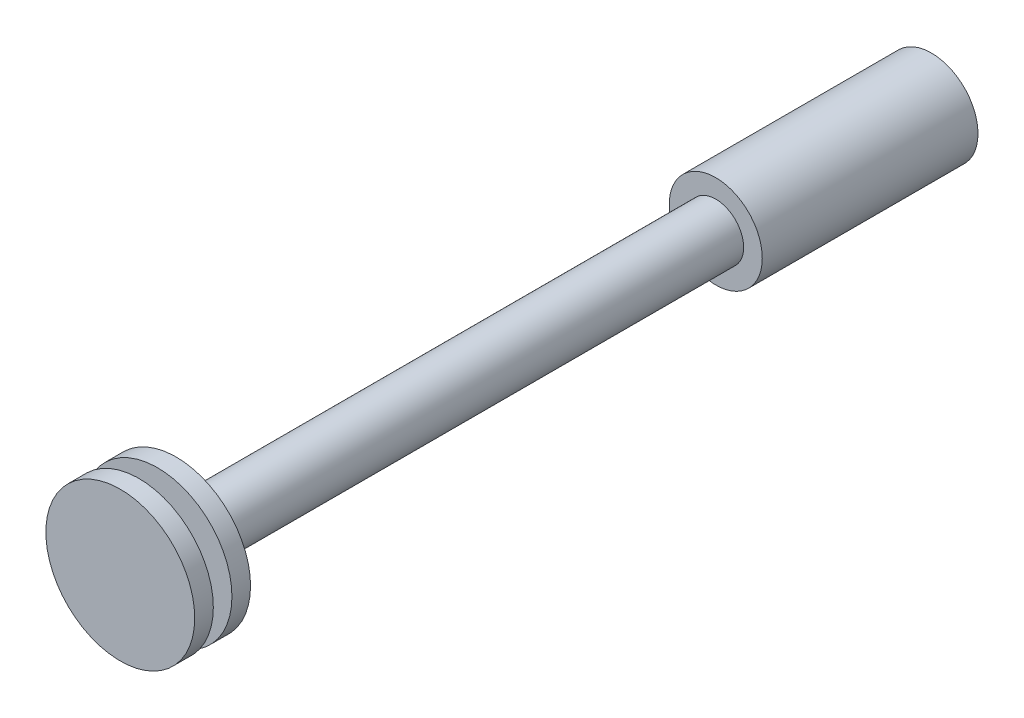
SolidWorks part; units mm, degrees
ref_plane "前视基准面" through (0, 0, 0) normal (0, 0, 1) x (1, 0, 0)
ref_plane "上视基准面" through (0, 0, 0) normal (0, 1, 0) x (1, 0, 0)
ref_plane "右视基准面" through (0, 0, 0) normal (1, 0, 0) x (0, 0, -1)
other "Configuration Table"
sketch "草图1" plane through (0, 0, 0) normal (0, 0, 1) x (1, 0, 0)
  circle A0 centre (0, 0) radius 3
extrude "凸台-拉伸1" add sketch "草图1" along normal blind 180
sketch "草图2" plane through (0, 0, 180) normal (0, 0, 1) x (1, 0, 0)
  circle A2 centre (0, 0) radius 8
  circle A3 centre (0, 0) radius 8
  dimension "D1" = 5
extrude "凸台-拉伸2" add sketch "草图2" against normal blind 2
extrude "凸台-拉伸3" add sketch "草图2<2>" along normal blind 2 from surface starting at face at (3, 0, 0)
sketch "草图2<2>" plane through (0, 0, 180) normal (0, 0, 1) x (1, 0, 0) same geometry as "草图2"
extrude "凸台-拉伸4" add sketch "草图1<2>" against normal blind 2
sketch "草图1<2>" plane through (0, 0, 0) normal (0, 0, 1) x (1, 0, 0) same geometry as "草图1"
extrude "凸台-拉伸5" add sketch "草图1<3>" along normal blind 2 from surface starting at face at (8, 0, 180)
sketch "草图1<3>" plane through (0, 0, 0) normal (0, 0, 1) x (1, 0, 0) same geometry as "草图1"
extrude "凸台-拉伸6" add sketch "草图2<3>" along normal blind 2 from surface starting at face at (3, 0, 182)
sketch "草图2<3>" plane through (0, 0, 180) normal (0, 0, 1) x (1, 0, 0) same geometry as "草图2"
extrude "凸台-拉伸7" add sketch "草图2<4>" against normal blind 2 from surface starting at face at (3, 0, -2)
sketch "草图2<4>" plane through (0, 0, 180) normal (0, 0, 1) x (1, 0, 0) same geometry as "草图2"
sketch "草图3" plane through (0, 0, 184) normal (0, 0, 1) x (1, 0, 0)
  circle A0 centre (0, 0) radius 5
extrude "凸台-拉伸10" add sketch "草图3" against normal blind 60 from offset 64 offset against normal yes
sketch "草图4" plane through (0, 0, 0) normal (1, 0, 0) x (0, 0, -1)
  line L1 (19.1288, 22.8607) -> (-96.8124, 22.8607)
  line L2 (19.1288, 22.8607) -> (19.1288, -22.3367)
  line L3 (19.1288, -22.3367) -> (-96.8124, -22.3367)
  line L4 (-96.8124, 22.8607) -> (-96.8124, -22.3367)
extrude "切除-拉伸1" cut sketch "草图4" against normal through all both and the other way through all
